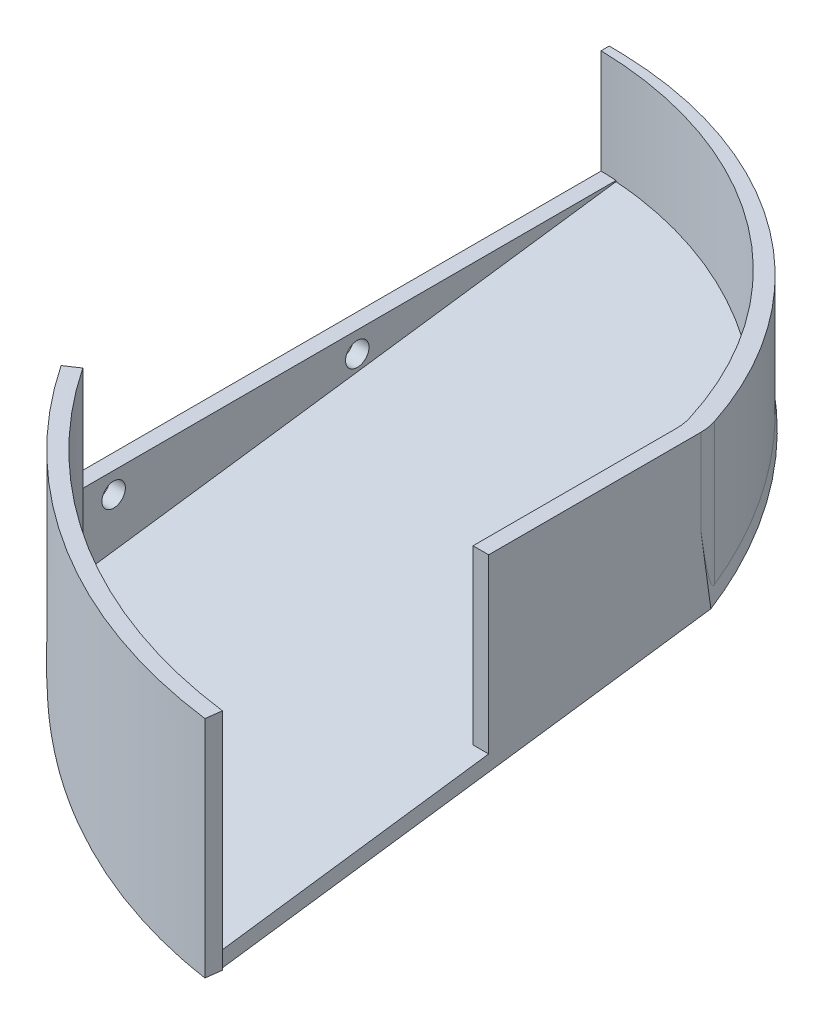
SolidWorks part; units mm, degrees
ref_plane "Front Plane" through (0, 0, 0) normal (0, 0, 1) x (1, 0, 0)
ref_plane "Top Plane" through (0, 0, 0) normal (0, 1, 0) x (1, 0, 0)
ref_plane "Right Plane" through (0, 0, 0) normal (1, 0, 0) x (0, 0, -1)
sketch "Sketch1" plane through (0, 0, 0) normal (1, 0, 0) x (0, 0, -1)
  line L0 (0, 0) -> (-150.2, -20.5184)
  line L1 (0, 0) -> (0, 3)
  line L2 (0, 3) -> (-150.2, 3)
  line L3 (-150.2, 3) -> (-150.2, -20.5184)
  dimension "D1" = 3
  dimension "D2" = 150.2
extrude "Boss-Extrude1" add sketch "Sketch1" along normal blind 3
sketch "Sketch2" plane through (0, 0, 0) normal (0, -0.9908, -0.1354) x (1, 0, 0)
  line L0 (3, 151.595) -> (0, 151.595) construction
  line L1 (3, 0) -> (73, 0)
  line L2 (3, 0) -> (3, 151.595)
  line L3 (3, 151.595) -> (73, 151.595)
  line L4 (73, 0) -> (73, 151.595)
  dimension "D1" = 70
extrude "Boss-Extrude2" add sketch "Sketch2" against normal blind 3
sketch "Sketch5" plane through (0, 3, 0) normal (0, 1, 0) x (1, 0, 0)
  line L0 (3, -104.0522) -> (0.5083, -105.723)
  line L1 (73, -150.6061) -> (73.3849, -147.6308)
  line L6 (70, -96.1466) -> (73, -96.1466)
  line L8 (3, 0) -> (3, -150.2) construction
  line L9 (3, -0.0595) -> (0, 0)
  line L10 (70, -96.1466) -> (70, -55.6681)
  line L11 (0, 0) -> (0, -1.5721)
  line L12 (73, -53.9086) -> (73, -96.1466)
  line L15 (73, -0.4061) -> (73, -150.6061) construction
  arc A0 (0.5083, -105.723) -> (73, -150.6061) centre (86.2426, -48.2346) ccw
  arc A1 (3, -104.0522) -> (73.3849, -147.6308) centre (86.2426, -48.2346) ccw
  arc A2 (0, -1.5721) -> (70, -55.6681) centre (-1.6608, -76.059) cw
  arc A3 (3, -0.0595) -> (73, -53.9086) centre (0.5055, -75.7242) cw
  point P9 (65, -54.7432)
  dimension "D3" = 42.238
  dimension "D2" = 3
  dimension "D1" = 3
extrude "Boss-Extrude3" add sketch "Sketch5" along normal blind 20 and the other way blind 30
sketch "Sketch6" plane through (0, 3, 0) normal (0, 1, 0) x (1, 0, 0)
  line L0 (0.5083, -105.723) -> (0, -105.723)
  line L1 (0, -1.5721) -> (0, -150.2) construction
  line L2 (0, -105.723) -> (0, -169.0514)
  line L4 (0, -169.0514) -> (84.9815, -167.5759)
  line L5 (84.9815, -167.5759) -> (85.3151, -151.4548)
  arc A0 (0.5083, -105.723) -> (73, -150.6061) centre (86.2426, -48.2346) ccw construction
  arc A1 (0.5083, -105.723) -> (85.3151, -151.4548) centre (86.2426, -48.2346) ccw
extrude "Cut-Extrude2" cut sketch "Sketch6" against normal blind 33
sketch "Sketch8" plane through (0, 2.9724, 0.4061) normal (0, 0.9908, 0.1354) x (1, 0, 0)
  line L0 (8.1574, 0) -> (3.866, 8.2167)
  line L1 (3.866, 8.2167) -> (75.7058, 9.4387)
  line L2 (75.7058, 9.4387) -> (81.7063, -54.8115)
  line L3 (81.7063, -54.8115) -> (73, -53.9995)
  ellipse E0 centre (0.5055, -76.0176) end of major axis (0.5055, -152.4266) minor radius 75.7058 (73, -53.9995) -> (8.1574, 0) ccw construction
  ellipse E1 centre (0.5055, -76.0176) end of major axis (0.5055, -152.4266) minor radius 75.7058 (73, -53.9995) -> (8.1574, 0) ccw
extrude "Cut-Extrude4" cut sketch "Sketch8" against normal blind 115
fillet "Fillet1" radius 10 1 edges at (70, 9.2116, 55.6681)
fillet "Fillet2" radius 10 1 edges at (73, 9.3318, 53.9086)
sketch "Sketch9" plane through (0, 0, 0) normal (0, -0.9908, -0.1354) x (1, 0, 0)
  line L4 (3, 0) -> (8.1574, 0)
  line L5 (3, 0) -> (8.1574, 0)
  line L6 (73, 53.9995) -> (73, 54.4093)
  line L7 (73, 53.9995) -> (73, 54.4093)
  line L8 (3, 0.06) -> (0, 0)
  line L10 (3, 0.06) -> (0, 0)
  line L11 (0, 0) -> (3, 0)
  line L12 (0, 0) -> (3, 0)
  ellipse E0 centre (61.7447, 142.3322) end of major axis (63.9947, 142.3322) minor radius 2.2293 construction
  ellipse E1 centre (61.7447, 142.3322) end of major axis (63.9947, 142.3322) minor radius 2.2293
  ellipse E3 centre (0.5055, 76.0176) end of major axis (0.5055, -0.3913) minor radius 75.7058 (8.1574, 0) -> (73, 53.9995) ccw
  ellipse E4 centre (0.5055, 76.0176) end of major axis (0.5055, -0.3913) minor radius 75.7058 (8.1574, 0) -> (73, 53.9995) ccw
  ellipse E5 centre (0.5055, 76.4275) end of major axis (0.5055, 0.0185) minor radius 75.7058 (3, 0.06) -> (73, 54.4093) ccw
  ellipse E7 centre (0.5055, 76.4275) end of major axis (0.5055, 0.0185) minor radius 75.7058 (3, 0.06) -> (73, 54.4093) ccw
  dimension "D1" = 0
extrude "Cut-Extrude6" cut sketch "Sketch9" against normal up to next contours E1
sketch "Sketch10" plane through (3, 0, 0) normal (1, 0, 0) x (0, 0, -1)
  line L0 (-1.6995, 3) -> (-104.0522, 3) construction
  circle A0 centre (-98.132, -1) radius 2.25
  circle A1 centre (-51.3666, -1) radius 2.25
  point P4 (0, 0)
  point P7 (-51.3666, -1)
  dimension "D1" = 4.5
  dimension "D2" = 4.5
  dimension "D3" = 4
extrude "Cut-Extrude7" cut sketch "Sketch10" against normal up to next
sketch "Sketch11" plane through (70, 0, 0) normal (-1, 0, 0) x (0, 0, 1)
  line L0 (1.5721, -0.2148) -> (55.6681, -7.6047) construction
  line L1 (55.6681, -7.6047) -> (96.1466, -13.1343) construction
  line L2 (1.5721, -0.2148) -> (55.6681, -7.6047)
  line L3 (55.6681, -7.6047) -> (96.1466, -13.1343)
  line L4 (96.1466, -13.1343) -> (96.1466, -41.8898)
  line L5 (96.1466, -41.8898) -> (-9.4828, -44.1872)
  line L6 (-9.4828, -44.1872) -> (-10.5115, 3.1101)
  line L7 (-10.5115, 3.1101) -> (1.5721, -0.2148)
extrude "Cut-Extrude8" cut sketch "Sketch11" against normal up to next and the other way blind 94
sketch "Sketch13" plane through (49.061, 0, 73.1664) normal (-0.5569, 0, -0.8306) x (-0.8306, 0, 0.5569)
  line L0 (21.5602, -20.1606) -> (25.0582, -40.8163)
  line L1 (25.0582, -40.8163) -> (81.1182, -31.3227)
  line L2 (81.1182, -31.3227) -> (73.6982, -14.2143)
  line L3 (73.6982, -14.2143) -> (55.4539, -14.3129)
  ellipse E0 centre (-44.7667, -6.5892) end of major axis (-144.9873, 1.1344) minor radius 11.3384 (21.5602, -20.1606) -> (55.4577, -14.2143) ccw construction
  ellipse E1 centre (-44.7667, -6.5892) end of major axis (-144.9873, 1.1344) minor radius 11.3384 (21.5602, -20.1606) -> (55.4577, -14.2143) ccw
  line M1 (58.4577, -14.4425) -> (55.4577, -14.2143)
  line M2 (55.4577, -14.2143) -> (55.4577, -27)
  line M3 (55.4577, -27) -> (58.4577, -27)
  line M4 (58.4577, -27) -> (58.4577, -14.4425)
extrude "Cut-Extrude10" cut sketch "Sketch13" against normal blind 103 contours E1 L0 L1 L2 L3 M1 M4 M3 M2 | L3 M1 M2 M3 M4 region at (7.619, -27.0448, 100.955) region at (1.7565, -20.6741, 104.886)
sketch "Sketch14" plane through (90.96, 0, 11.7664) normal (0.9917, 0, 0.1283) x (0.1283, 0, -0.9917)
  line L0 (-139.6292, -20.123) -> (-133.4751, -20.123)
  line L1 (-133.4751, -20.123) -> (-133.4751, -31.4571)
  line L2 (-133.4751, -31.4571) -> (-143.1751, -29.8406)
  line L3 (-143.1751, -29.8406) -> (-139.6292, -20.123)
  arc A0 (-139.9964, -20.1161) -> (-137.4389, -20.1606) centre (-124.2532, 811.8598) ccw construction
extrude "Cut-Extrude11" cut sketch "Sketch14" against normal blind 103
